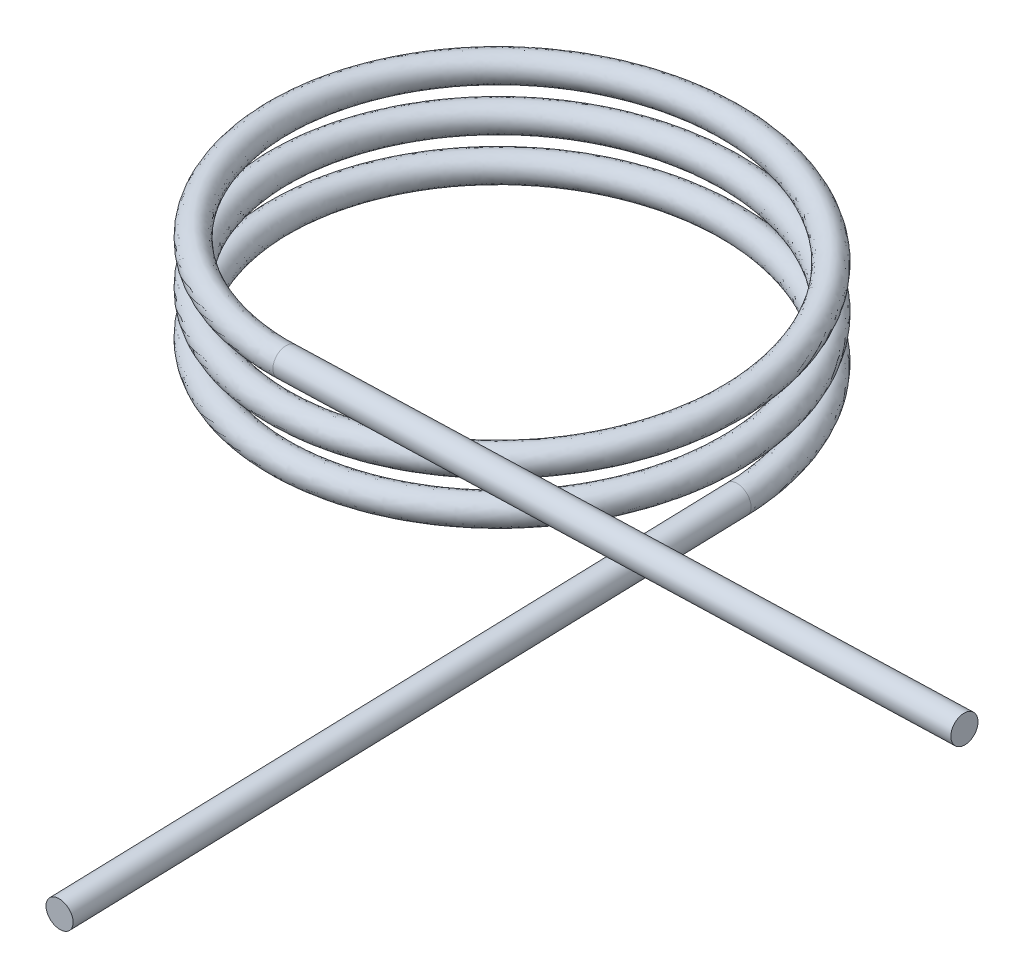
SolidWorks part; units mm, degrees
note: '?' marks a value the reader was unsure of.
ref_plane "Front Plane" through (0, 0, 0) normal (0, 0, 1) x (1, 0, 0)
ref_plane "Top Plane" through (0, 0, 0) normal (0, 1, 0) x (1, 0, 0)
ref_plane "Right Plane" through (0, 0, 0) normal (1, 0, 0) x (0, 0, -1)
sketch "Sketch2" plane through (0, 0, 0) normal (0, 1, 0) x (1, 0, 0)
  circle A0 centre (0, 0) radius 33.782
  dimension "D1" = 67.564
curve "Helix/Spiral1" pitch 6.477 height 17.8117 turns 2.75
sweep "Sweep1" add path "Helix/Spiral1" circular profile diameter 4.064 parameters "D3"=4.064
sketch "Sketch15" plane through (0.543, 0.0166, 0) normal (0.9995, 0.0305, 0) x (0, 0, -1)
  circle A1 centre (-33.782, 17.8035) radius 2.032
  circle A2 centre (-33.782, 17.8035) radius 2.032
  dimension "D1" = 0
extrude "Boss-Extrude1" add sketch "Sketch15" along normal blind 101.6
sketch "Sketch24" plane through (0, 0, 0) normal (0, -0.0305, 0.9995) x (1, 0, 0)
  circle A1 centre (33.782, 0) radius 2.032
  circle A2 centre (33.782, 0) radius 2.032
  dimension "D1" = 0
extrude "Boss-Extrude2" add sketch "Sketch24" along normal blind 101.6
ref_axis "Axis1" through (0, 50.5632, 0) along (0, -1, 0)?
